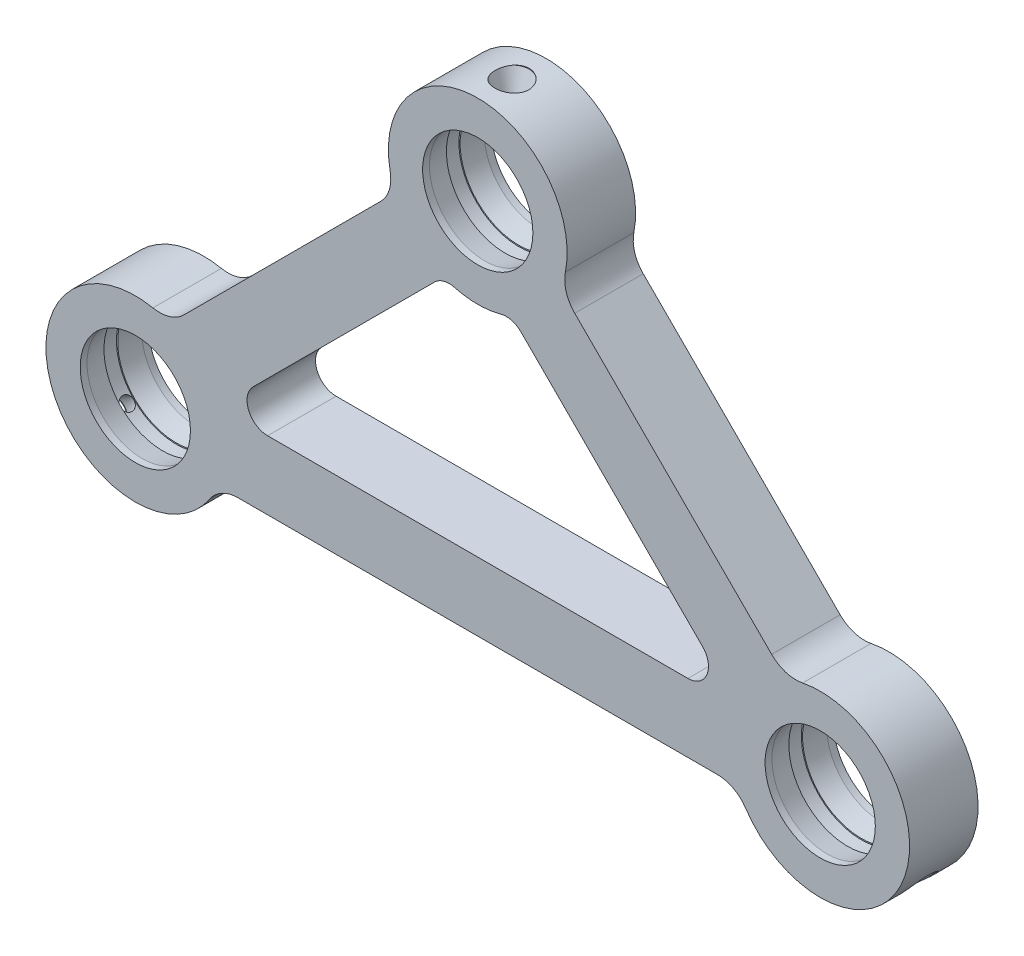
SolidWorks part; units mm, degrees
ref_plane "Front Plane" through (0, 0, 0) normal (0, 0, 1) x (1, 0, 0)
ref_plane "Top Plane" through (0, 0, 0) normal (0, 1, 0) x (1, 0, 0)
ref_plane "Right Plane" through (0, 0, 0) normal (1, 0, 0) x (0, 0, -1)
sketch "Sketch1" plane through (0, 0, 0) normal (0, 0, 1) x (1, 0, 0)
  line L0 (-26.538, 0) -> (73.462, 0) construction
  line L2 (-26.538, 0) -> (23.462, 50) construction
  line L3 (23.462, 50) -> (73.462, 0) construction
  line L4 (-14.4839, 5) -> (61.4078, 5)
  line L5 (-14.4839, -5) -> (61.4078, -5)
  line L6 (-21.55, 12.0591) -> (11.4029, 45.012)
  line L7 (18.474, 37.9409) -> (-14.4789, 4.988)
  line L8 (28.45, 37.9409) -> (61.4029, 4.988)
  line L9 (35.5211, 45.012) -> (68.474, 12.0591)
  circle A0 centre (23.462, 50) radius 8.05
  circle A1 centre (73.462, 0) radius 8.05
  circle A2 centre (-26.538, 0) radius 8.05
  circle A3 centre (-26.538, 0) radius 13.05
  circle A4 centre (23.462, 50) radius 13.05
  circle A5 centre (73.462, 0) radius 13.05
  dimension "D1" = 16.1
  dimension "D2" = 16.1
  dimension "D3" = 16.1
  dimension "D4" = 45
  dimension "D5" = 45
  dimension "D6" = 100
  dimension "D7" = 5
  dimension "D8" = 5
  dimension "D9" = 5
  dimension "D10" = 5
  dimension "D11" = 5
  dimension "D12" = 5
  dimension "D13" = 5
  dimension "D14" = 5
  dimension "D15" = 5
extrude "Boss-Extrude1" add sketch "Sketch1" along normal blind 8 contours A3 A2 | A4 L6 A3 L4 L7 | A4 A0 | A5 L9 A4 L8 L4 | A5 L8 L4 L7 A3 L5 | A5 A1 | A3 L7 L4 | A5 L4 L8 region at (-1.538, 25, 0) region at (-14.4766, 4.996, 0) region at (-14.8224, 4.8528, 0) region at (23.462, 0, 0) region at (48.462, 25, 0) region at (61.4006, 4.996, 0) region at (14.4953, 41.0333, 0) region at (64.4997, 8.9712, 0)
sketch3d "3DSketch1" plane through (0, 0, 0) normal (0, 0, 1) x (1, 0, 0)
  dimension "D1" = 4
sketch "Sketch3" plane through (0, 0, 4) normal (0, 0, 1) x (1, 0, 0)
  circle A0 centre (-26.538, 0) radius 8.7553
  circle A1 centre (23.462, 50) radius 8.7553
  circle A2 centre (73.462, 0) radius 8.7553
  circle A3 centre (-26.538, 0) radius 8.05 construction
  circle A4 centre (23.462, 50) radius 8.05 construction
  circle A5 centre (73.462, 0) radius 8.05 construction
  dimension "D1" = 0.7053
  dimension "D2" = 0.7053
  dimension "D3" = 0.7053
extrude "Cut-Extrude1" cut sketch "Sketch3" against normal blind 1 and the other way blind 1 contours A1 | A0 | A2
sketch3d "3DSketch2" plane through (0, 0, 0) normal (0, 0, 1) x (1, 0, 0)
sketch3d "3DSketch3" plane through (0, 0, 0) normal (0, 0, 1) x (1, 0, 0)
  dimension "D1" = 26
sketch "Sketch4" plane through (0, 62.95, 0) normal (0, -1, 0) x (-1, 0, 0)
  line L0 (-41.8, -4) -> (41.8, -4) construction
  line L1 (-86.512, 0) -> (-86.512, -8) construction
  line L4 (-36.5118, -8) -> (-68.474, -8)
  line L5 (-36.5118, -8) -> (-68.474, -8)
  line L6 (-68.474, -8) -> (-86.512, -8)
  line L7 (-68.474, -8) -> (-86.512, -8)
  line L8 (-86.512, -8) -> (-86.512, 0)
  line L9 (-86.512, -8) -> (-86.512, 0)
  line L10 (-86.512, 0) -> (-68.474, 0)
  line L11 (-86.512, 0) -> (-68.474, 0)
  line L12 (-68.474, 0) -> (-36.5118, 0)
  line L13 (-68.474, 0) -> (-36.5118, 0)
  line L14 (-36.5118, 0) -> (-10.4122, 0)
  line L15 (-36.5118, 0) -> (-10.4122, 0)
  line L16 (-10.4122, 0) -> (21.55, 0)
  line L17 (-10.4122, 0) -> (21.55, 0)
  line L18 (21.55, 0) -> (39.588, 0)
  line L19 (21.55, 0) -> (39.588, 0)
  line L20 (39.588, 0) -> (39.588, -8)
  line L21 (39.588, 0) -> (39.588, -8)
  line L22 (39.588, -8) -> (21.55, -8)
  line L23 (39.588, -8) -> (21.55, -8)
  line L24 (21.55, -8) -> (-10.4122, -8)
  line L25 (21.55, -8) -> (-10.4122, -8)
  line L26 (-10.4122, -8) -> (-36.5118, -8)
  line L27 (-10.4122, -8) -> (-36.5118, -8)
  circle A0 centre (-23.462, -4) radius 2.5
  dimension "D1" = 5
  dimension "D2" = 63.05
  dimension "D3" = 126.1
extrude "Cut-Extrude2" cut sketch "Sketch4" along normal blind 6 draft 20 and the other way blind 10 contours A0
fillet "Fillet1" radius 3 4 edges at (-14.4669, 5, 4) (18.474, 37.9409, 4) (28.45, 37.9409, 4) (61.3909, 5, 4)
fillet "Fillet2" radius 5 6 edges at (68.474, 12.0591, 4) (35.5211, 45.012, 4) (11.4029, 45.012, 4) (-21.55, 12.0591, 4) (-14.4839, -5, 4) (61.4078, -5, 4)
sketch3d "3DSketch4" plane through (0, 0, 0) normal (0, 0, 1) x (1, 0, 0)
sketch3d "3DSketch5" plane through (0, 0, 0) normal (0, 0, 1) x (1, 0, 0)
  dimension "D1" = 26
sketch "Sketch5" plane through (45.888, -45.888, 0) normal (-0.7071, 0.7071, 0) x (0, 0, 1)
  line L0 (8, -31.8152) -> (8, -7.901) construction
  line L1 (8, 43.8955) -> (8, 59.9955) construction
  line L2 (8, 43.8955) -> (8, 59.9955)
  line L7 (8, 64.9955) -> (0, 64.9955) construction
  line L8 (8, 64.9955) -> (0, 64.9955)
  circle A0 centre (4, 51.9455) radius 2.5
  dimension "D1" = 5
  dimension "D2" = 4
  dimension "D3" = 8.05
  dimension "D4" = 16.1
extrude "Cut-Extrude3" cut sketch "Sketch5" along normal blind 6 draft 20 and the other way blind 10 contours A0 region at (82.619, -9.157, 4)
draft "Draft4" type of draft neutral plane draft angle 10 faces to draft 3 face at (-18.488, 0, 5) face at (31.512, 50, 5) face at (81.512, 0, 5) neutral plane through (0, 0, 8) neutral plane normal (0, 0, 1) reverse direction yes parameters "D1"=10
draft "Draft6" type of draft neutral plane draft angle 10 faces to draft 3 face at (-18.488, 0, 0) face at (81.512, 0, 0) face at (31.512, 50, 0) neutral plane through (0, 0, 0) neutral plane normal (0, 0, -1) reverse direction yes parameters "D1"=10
sketch3d "3DSketch6" plane through (0, 0, 0) normal (0, 0, 1) x (1, 0, 0)
sketch3d "3DSketch8" plane through (0, 0, 0) normal (0, 0, 1) x (1, 0, 0)
  dimension "D1" = 26
sketch "Sketch6" plane through (-22.426, -22.426, 0) normal (0.7071, 0.7071, 0) x (0, 0, -1)
  line L0 (-8, 31.8152) -> (-8, 5.7152) construction
  line L1 (0, 31.8152) -> (-8, 31.8152) construction
  line L2 (0, 31.8152) -> (-8, 31.8152)
  line L3 (0, 10.7152) -> (0, 26.8152) construction
  line L4 (0, 10.7152) -> (0, 26.8152)
  circle A0 centre (-4, 18.7652) radius 2.5
  dimension "D1" = 5
  dimension "D2" = 4
  dimension "D4" = 16.1
  dimension "D5" = 8.05
extrude "Cut-Extrude4" cut sketch "Sketch6" along normal blind 10 draft 20 and the other way blind 10 contours A0
sketch "Sketch7" plane through (0, 0, 8) normal (0, 0, 1) x (1, 0, 0)
  line L2 (-7.2243, 5) -> (54.1483, 5) construction
  line L5 (17.1588, 36.6257) -> (-9.3456, 10.1213) construction
  line L10 (29.7652, 36.6257) -> (56.2696, 10.1213) construction
  line L11 (66.372, 14.161) -> (37.623, 42.91)
  line L12 (9.301, 42.91) -> (-19.448, 14.161)
  line L13 (-11.5113, -5) -> (58.4353, -5)
  line L14 (66.372, 14.161) -> (37.623, 42.91)
  line L15 (9.301, 42.91) -> (-19.448, 14.161)
  line L16 (-11.5113, -5) -> (58.4353, -5)
  line L17 (-7.2243, 5) -> (54.1483, 5)
  line L18 (17.1588, 36.6257) -> (-9.3456, 10.1213)
  line L19 (29.7652, 36.6257) -> (56.2696, 10.1213)
  circle A36 centre (-26.538, 0) radius 8.05 construction
  arc A37 (-9.3456, 10.1213) -> (-7.2243, 5) centre (-7.2243, 8) ccw construction
  arc A38 (54.1483, 5) -> (56.2696, 10.1213) centre (54.1483, 8) ccw construction
  circle A39 centre (73.462, 0) radius 8.05 construction
  circle A40 centre (23.462, 50) radius 8.05 construction
  arc A41 (29.7652, 36.6257) -> (26.8622, 37.4008) centre (27.6439, 34.5044) ccw construction
  arc A42 (20.0618, 37.4008) -> (26.8622, 37.4008) centre (23.462, 50) ccw construction
  arc A43 (20.0618, 37.4008) -> (17.1588, 36.6257) centre (19.2801, 34.5044) ccw construction
  circle A44 centre (-26.538, 0) radius 8.05
  arc A45 (36.2565, 47.4302) -> (37.623, 42.91) centre (41.1586, 46.4456) ccw
  arc A46 (36.2565, 47.4302) -> (10.6675, 47.4302) centre (23.462, 50) ccw
  arc A47 (9.301, 42.91) -> (10.6675, 47.4302) centre (5.7654, 46.4456) ccw
  arc A48 (-23.9682, 12.7945) -> (-19.448, 14.161) centre (-22.9836, 17.6966) ccw
  arc A49 (-23.9682, 12.7945) -> (-15.6738, -7.2299) centre (-26.538, 0) ccw
  arc A50 (-11.5113, -5) -> (-15.6738, -7.2299) centre (-11.5113, -10) ccw
  arc A51 (62.5978, -7.2299) -> (58.4353, -5) centre (58.4353, -10) ccw
  arc A52 (62.5978, -7.2299) -> (70.8922, 12.7945) centre (73.462, 0) ccw
  arc A53 (66.372, 14.161) -> (70.8922, 12.7945) centre (69.9076, 17.6966) ccw
  arc A54 (36.2565, 47.4302) -> (37.623, 42.91) centre (41.1586, 46.4456) ccw
  arc A55 (36.2565, 47.4302) -> (10.6675, 47.4302) centre (23.462, 50) ccw
  arc A56 (9.301, 42.91) -> (10.6675, 47.4302) centre (5.7654, 46.4456) ccw
  arc A57 (-23.9682, 12.7945) -> (-19.448, 14.161) centre (-22.9836, 17.6966) ccw
  arc A58 (-23.9682, 12.7945) -> (-15.6738, -7.2299) centre (-26.538, 0) ccw
  arc A59 (-11.5113, -5) -> (-15.6738, -7.2299) centre (-11.5113, -10) ccw
  arc A60 (62.5978, -7.2299) -> (58.4353, -5) centre (58.4353, -10) ccw
  arc A61 (62.5978, -7.2299) -> (70.8922, 12.7945) centre (73.462, 0) ccw
  arc A62 (66.372, 14.161) -> (70.8922, 12.7945) centre (69.9076, 17.6966) ccw
  arc A63 (-9.3456, 10.1213) -> (-7.2243, 5) centre (-7.2243, 8) ccw
  arc A64 (54.1483, 5) -> (56.2696, 10.1213) centre (54.1483, 8) ccw
  circle A65 centre (73.462, 0) radius 8.05
  circle A66 centre (23.462, 50) radius 8.05
  arc A67 (29.7652, 36.6257) -> (26.8622, 37.4008) centre (27.6439, 34.5044) ccw
  arc A68 (20.0618, 37.4008) -> (26.8622, 37.4008) centre (23.462, 50) ccw
  arc A69 (20.0618, 37.4008) -> (17.1588, 36.6257) centre (19.2801, 34.5044) ccw
  dimension "D1" = 0
extrude "Boss-Extrude3" add sketch "Sketch7" along normal blind 1
sketch "Sketch11" plane through (0, 0, 0) normal (0, 0, -1) x (-1, 0, 0)
  line L0 (-29.7652, 36.6257) -> (-56.2696, 10.1213) construction
  line L1 (7.2243, 5) -> (-54.1483, 5) construction
  line L2 (-17.1588, 36.6257) -> (9.3456, 10.1213) construction
  line L3 (-37.623, 42.91) -> (-66.372, 14.161)
  line L4 (-58.4353, -5) -> (11.5113, -5)
  line L5 (19.448, 14.161) -> (-9.301, 42.91)
  line L6 (-37.623, 42.91) -> (-66.372, 14.161)
  line L7 (-58.4353, -5) -> (11.5113, -5)
  line L8 (19.448, 14.161) -> (-9.301, 42.91)
  line L9 (-17.1588, 36.6257) -> (9.3456, 10.1213)
  line L10 (7.2243, 5) -> (-54.1483, 5)
  line L11 (-29.7652, 36.6257) -> (-56.2696, 10.1213)
  circle A0 centre (-23.462, 50) radius 8.05 construction
  circle A1 centre (-73.462, 0) radius 8.05
  circle A2 centre (-73.462, 0) radius 8.05
  circle A3 centre (-23.462, 50) radius 8.05
  circle A4 centre (26.538, 0) radius 8.05 construction
  circle A5 centre (26.538, 0) radius 8.05
  arc A6 (-17.1588, 36.6257) -> (-20.0618, 37.4008) centre (-19.2801, 34.5044) ccw construction
  arc A7 (-26.8622, 37.4008) -> (-20.0618, 37.4008) centre (-23.462, 50) ccw construction
  arc A8 (-26.8622, 37.4008) -> (-29.7652, 36.6257) centre (-27.6439, 34.5044) ccw construction
  arc A9 (-56.2696, 10.1213) -> (-54.1483, 5) centre (-54.1483, 8) ccw construction
  arc A10 (7.2243, 5) -> (9.3456, 10.1213) centre (7.2243, 8) ccw construction
  arc A11 (-10.6675, 47.4302) -> (-36.2565, 47.4302) centre (-23.462, 50) ccw
  arc A12 (-37.623, 42.91) -> (-36.2565, 47.4302) centre (-41.1586, 46.4456) ccw
  arc A13 (-70.8922, 12.7945) -> (-66.372, 14.161) centre (-69.9076, 17.6966) ccw
  arc A14 (-70.8922, 12.7945) -> (-62.5978, -7.2299) centre (-73.462, 0) ccw
  arc A15 (-58.4353, -5) -> (-62.5978, -7.2299) centre (-58.4353, -10) ccw
  arc A16 (15.6738, -7.2299) -> (11.5113, -5) centre (11.5113, -10) ccw
  arc A17 (15.6738, -7.2299) -> (23.9682, 12.7945) centre (26.538, 0) ccw
  arc A18 (19.448, 14.161) -> (23.9682, 12.7945) centre (22.9836, 17.6966) ccw
  arc A19 (-10.6675, 47.4302) -> (-9.301, 42.91) centre (-5.7654, 46.4456) ccw
  arc A20 (-10.6675, 47.4302) -> (-36.2565, 47.4302) centre (-23.462, 50) ccw
  arc A21 (-37.623, 42.91) -> (-36.2565, 47.4302) centre (-41.1586, 46.4456) ccw
  arc A22 (-70.8922, 12.7945) -> (-66.372, 14.161) centre (-69.9076, 17.6966) ccw
  arc A23 (-70.8922, 12.7945) -> (-62.5978, -7.2299) centre (-73.462, 0) ccw
  arc A24 (-58.4353, -5) -> (-62.5978, -7.2299) centre (-58.4353, -10) ccw
  arc A25 (15.6738, -7.2299) -> (11.5113, -5) centre (11.5113, -10) ccw
  arc A26 (15.6738, -7.2299) -> (23.9682, 12.7945) centre (26.538, 0) ccw
  arc A27 (19.448, 14.161) -> (23.9682, 12.7945) centre (22.9836, 17.6966) ccw
  arc A28 (-10.6675, 47.4302) -> (-9.301, 42.91) centre (-5.7654, 46.4456) ccw
  arc A29 (7.2243, 5) -> (9.3456, 10.1213) centre (7.2243, 8) ccw
  arc A30 (-56.2696, 10.1213) -> (-54.1483, 5) centre (-54.1483, 8) ccw
  arc A31 (-26.8622, 37.4008) -> (-29.7652, 36.6257) centre (-27.6439, 34.5044) ccw
  arc A32 (-26.8622, 37.4008) -> (-20.0618, 37.4008) centre (-23.462, 50) ccw
  arc A33 (-17.1588, 36.6257) -> (-20.0618, 37.4008) centre (-19.2801, 34.5044) ccw
  dimension "D1" = 0
  dimension "D2" = 0
extrude "Boss-Extrude4" add sketch "Sketch11" along normal blind 1
equation "\"D2@Sketch1\"=\"D1@Sketch1\""
equation "\"D3@Sketch1\"=\"D1@Sketch1\""
equation "\"D5@Sketch1\"=\"D4@Sketch1\""
equation "\"D8@Sketch1\"=\"D7@Sketch1\""
equation "\"D9@Sketch1\"=\"D7@Sketch1\""
equation "\"D11@Sketch1\"=\"D10@Sketch1\""
equation "\"D12@Sketch1\"=\"D10@Sketch1\""
equation "\"D13@Sketch1\"=\"D10@Sketch1\""
equation "\"D14@Sketch1\"=\"D13@Sketch1\""
equation "\"D15@Sketch1\"=\"D14@Sketch1\""
equation "\"D2@Sketch3\"=\"D1@Sketch3\""
equation "\"D3@Sketch3\"=\"D1@Sketch3\""
equation "\"D2@Sketch4\"=\"D3@Sketch4\"/2"
equation "\"D3@Sketch5\"=\"D4@Sketch5\"/2"
equation "\"D2@Sketch5\"=\"D5@Sketch5\"/2"
equation "\"D2@Sketch6\"=\"D3@Sketch6\"/2"
equation "\"D5@Sketch6\"=\"D4@Sketch6\"/2"
equation "\"D1@Sketch3\"=4*tan(10)"
